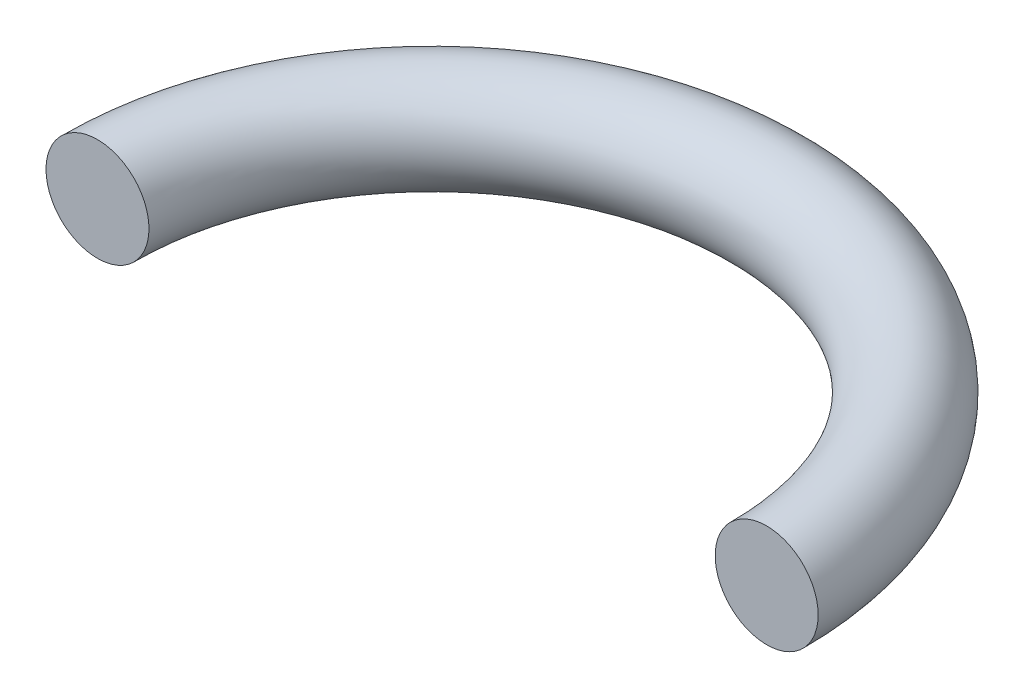
SolidWorks part; units mm, degrees
ref_plane "Front Plane" through (0, 0, 0) normal (0, 0, 1) x (1, 0, 0)
ref_plane "Top Plane" through (0, 0, 0) normal (0, 1, 0) x (1, 0, 0)
ref_plane "Right Plane" through (0, 0, 0) normal (1, 0, 0) x (0, 0, -1)
sketch "Sketch1" plane through (0, 0, 0) normal (0, 0, 1) x (1, 0, 0)
  line L0 (0, 0) -> (0, 29.1868) construction
  circle A0 centre (-26, 0) radius 4
  point P2 (-26, 0)
  point P6 (26, 0)
  dimension "D1" = 8
  dimension "D2" = 26
revolve "Revolve1" add sketch "Sketch1" angle 180 about L0 reverse direction yes
ref_axis "Axis1" through (-26, 0, 0) along (0, 0, 1)
ref_axis "Axis2" through (26, 0, 0) along (0, 0, 1)
